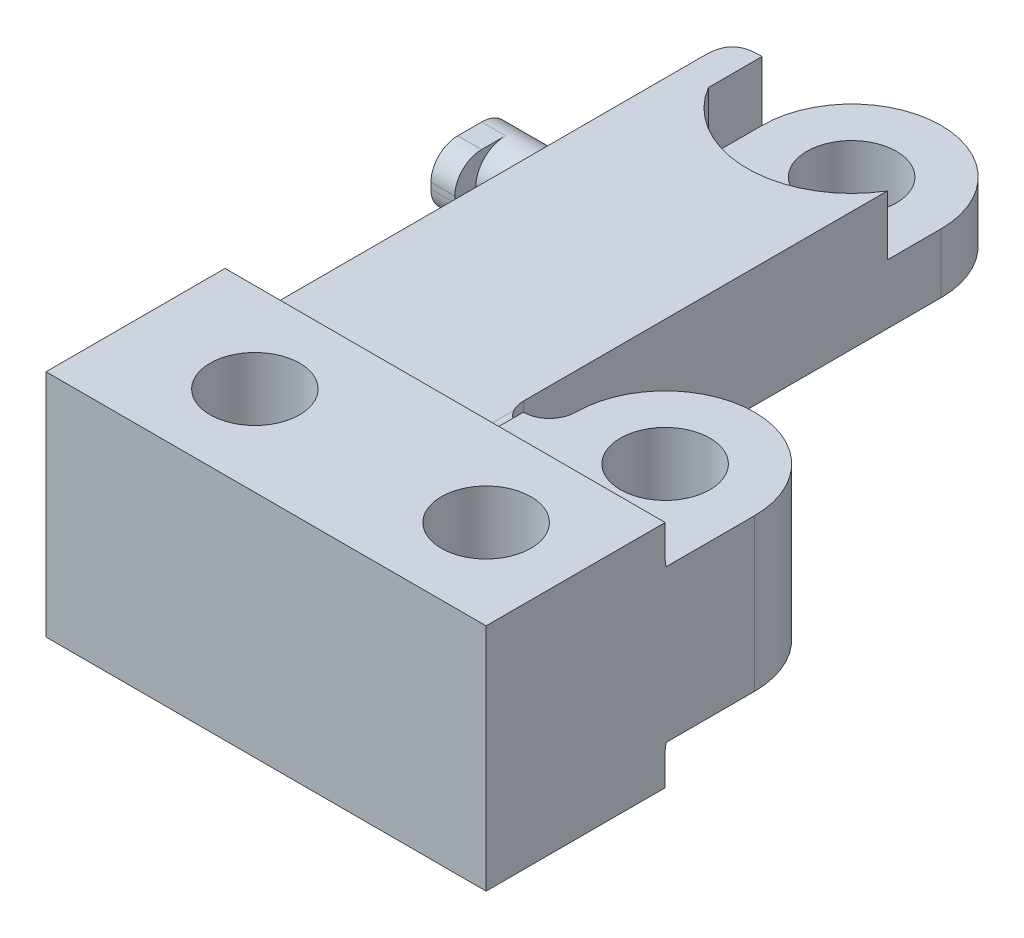
SolidWorks part; units mm, degrees
ref_plane "Front Plane" through (0, 0, 0) normal (0, 0, 1) x (1, 0, 0)
ref_plane "Top Plane" through (0, 0, 0) normal (0, 1, 0) x (1, 0, 0)
ref_plane "Right Plane" through (0, 0, 0) normal (1, 0, 0) x (0, 0, -1)
sketch "Sketch2" plane through (0, 0, 0) normal (0, 1, 0) x (1, 0, 0)
  line L0 (-6.875, 0) -> (6.875, 0)
  line L1 (-6.875, -6) -> (6.875, -6)
  line L2 (-6.875, -6) -> (-6.875, 6)
  line L5 (-6.875, -6) -> (6.875, 6) construction
  line L6 (-6.875, 6) -> (6.875, -6) construction
  line L7 (-0.875, 6) -> (-0.875, 17)
  line L9 (-6.875, 17) -> (-6.875, 6)
  line L10 (0, -8.1975) -> (0, 6) construction
  line L11 (6.875, 6) -> (-0.875, 6) construction
  line L12 (-3.875, -3) -> (-3.875, 20) construction
  line L13 (-0.875, 3) -> (-0.875, 6)
  line L14 (6.875, 3) -> (-0.875, 3) construction
  line L15 (6.875, 3) -> (6.875, -6)
  line L16 (6.875, 3) -> (6.875, 6) construction
  line L17 (0, 0) -> (0, 2.125)
  circle A4 centre (3.875, -3) radius 1.5
  circle A5 centre (3.875, 3) radius 1.5
  circle A6 centre (-3.875, -3) radius 1.5
  circle A7 centre (-3.875, 17) radius 1.5
  arc A8 (-6.875, 17) -> (-0.875, 17) centre (-3.875, 17) cw
  arc A9 (6.875, 3) -> (0.875, 3) centre (3.875, 3) ccw
  arc A10 (0.875, 3) -> (-0.875, 3) centre (0, 3) cw
  point P0 (0, 0)
  dimension "D3" = 3
  dimension "D4" = 3
  dimension "D8" = 3
  dimension "D1" = 13.75
  dimension "D2" = 12
  dimension "D5" = 3
  dimension "D6" = 3
  dimension "D7" = 7.75
  dimension "D9" = 20
extrude "Boss-Extrude1" add sketch "Sketch2" along normal mid plane 7.7 contours L15 L0 L2 L1 A6 A4 region at (0, 0, 3)
extrude "Boss-Extrude2" add sketch "Sketch2<4>" along normal mid plane 4 contours L17 A10 L13 L7 A8 L9 L2 L0 A7 region at (-3.8127, 0, -9.0692)
sketch "Sketch2<4>" plane through (0, 0, 0) normal (0, 1, 0) x (1, 0, 0) same geometry as "Sketch2"
extrude "Boss-Extrude3" add sketch "Sketch2<6>" along normal mid plane 5.1 contours A9 A10 L17 L0 L15 A5 region at (0.0912, 0, -1.0625)
sketch "Sketch2<6>" plane through (0, 0, 0) normal (0, 1, 0) x (1, 0, 0) same geometry as "Sketch2"
sketch "Sketch3" plane through (0, 2, 0) normal (0, 1, 0) x (1, 0, 0)
  line L0 (-6.875, 13.5) -> (-0.875, 13.5) construction
  line L1 (-6.875, 17) -> (-6.875, 0) construction
  line L2 (-0.875, 3) -> (-0.875, 17) construction
  line L3 (-6.875, 13.5) -> (-6.875, 17) construction
  line L4 (-0.875, 17) -> (-0.875, 13.5) construction
  line L5 (-6.875, 15.1972) -> (-6.875, 17)
  line L6 (-0.875, 15.1972) -> (-0.875, 17)
  circle A0 centre (-3.875, 17) radius 1.5 construction
  arc A1 (-6.875, 17) -> (-0.875, 17) centre (-3.875, 17) cw
  arc A2 (-0.875, 17) -> (-6.875, 17) centre (-3.875, 17) ccw construction
  arc A3 (-0.875, 15.1972) -> (-6.875, 15.1972) centre (-3.875, 17) cw
  dimension "D1" = 3.5
extrude "Cut-Extrude1" cut sketch "Sketch3" against normal blind 2
fillet "Fillet1" radius 0.8 2 edges at (-3.4375, -2, 0) (-3.4375, 2, 0)
fillet "Fillet2" radius 0.8 2 edges at (0, 2, -1.4625) (0, -2, -1.4625)
sketch "Sketch5" plane through (-6.875, 0, 0) normal (-1, 0, 0) x (0, 0, 1)
  line L0 (0, -3.85) -> (0, -2.8)
  line L1 (-0.8, -2) -> (-17, -2)
  line L2 (-15.1972, 2) -> (-20.7248, 2) construction
  line L3 (-17, -2) -> (-17, 2)
  line L4 (-17, 2) -> (-0.8, 2)
  line L5 (0, -3.85) -> (6, -3.85)
  line L6 (6, -3.85) -> (6, 3.85)
  line L7 (6, 3.85) -> (0, 3.85)
  line L8 (0, 3.85) -> (0, 2.8)
  line L9 (-17, -2.662) -> (-17, 3.85) construction
  arc A0 (0, 2.8) -> (-0.8, 2) centre (-0.8, 2.8) cw
  arc A1 (-0.8, -2) -> (0, -2.8) centre (-0.8, -2.8) cw
extrude "Boss-Extrude4" add sketch "Sketch5" along normal blind 1
fillet "Fillet4" radius 1 1 edges at (-7.875, 0, -17) curvature continuous yes
sketch "Sketch6" plane through (-7.875, 0, 0) normal (-1, 0, 0) x (0, 0, 1)
  line L0 (-20, 1.687) -> (-20, -3.8532) construction
  line L1 (-17, 2) -> (-17, -3.8532) construction
  line L2 (-14, 1.687) -> (-14, -3.8532) construction
  line L3 (-21.9328, 0) -> (-0.3669, 0) construction
  circle A0 centre (-11.4, 0) radius 1
  dimension "D1" = 2
  dimension "D2" = 6
  dimension "D3" = 2.6
extrude "Boss-Extrude5" add sketch "Sketch6" along normal blind 2
sketch "Sketch7" plane through (-9.875, 0, 0) normal (-1, 0, 0) x (0, 0, 1)
  line L0 (-11.4, 1) -> (-10.6, 1)
  line L1 (-9.7, 0.1) -> (-9.7, -0.1)
  line L2 (-10.6, -1) -> (-11.4, -1)
  line L3 (-16, 2) -> (-16, -2) construction
  circle A0 centre (-11.4, 0) radius 1 construction
  circle A1 centre (-11.4, 0) radius 1 construction
  arc A2 (-10.6, -1) -> (-9.7, -0.1) centre (-10.6, -0.1) ccw
  arc A3 (-10.6, 1) -> (-9.7, 0.1) centre (-10.6, 0.1) cw
  arc A4 (-11.4, 1) -> (-11.4, -1) centre (-11.4, 0) ccw
  circle M4 centre (-11.4, 0) radius 1
  dimension "D1" = 0.9
  dimension "D3" = 4.6
  dimension "D2" = 0.8
extrude "Boss-Extrude6" add sketch "Sketch7" along normal blind 0.8 contours A3 L0 L2 A2 L1 M4 | M4 region at (-9.875, 0, -11.4) region at (-9.875, 0, -10.2511)
